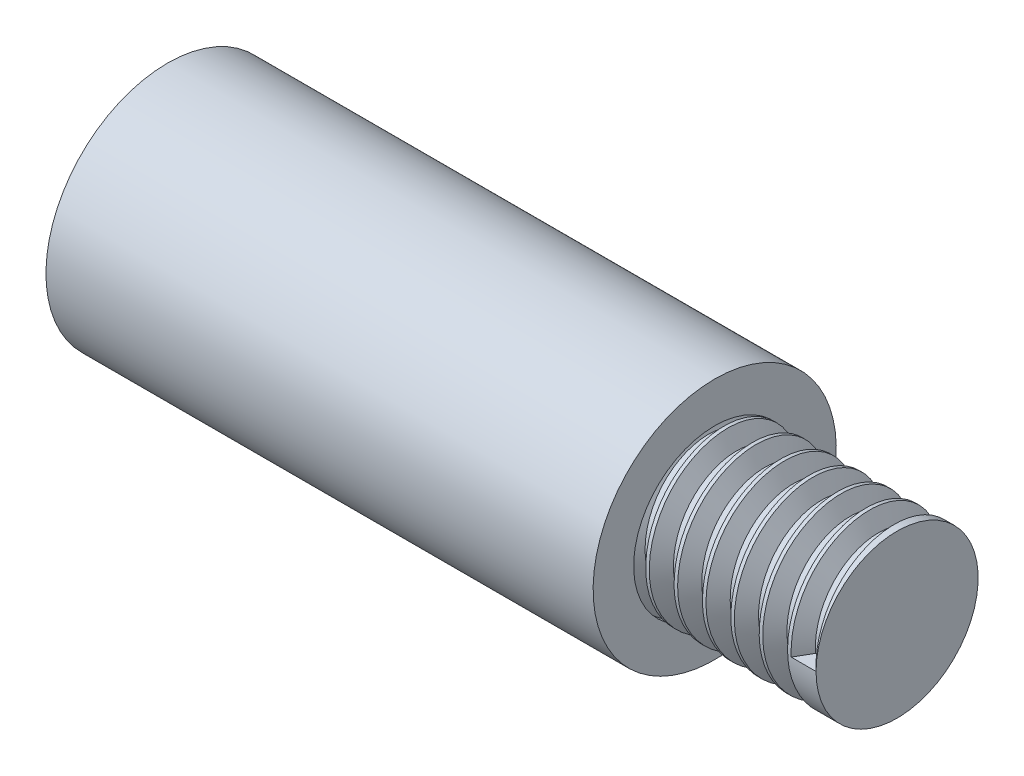
SolidWorks part; units mm, degrees
ref_plane "Front Plane" through (0, 0, 0) normal (0, 0, 1) x (1, 0, 0)
ref_plane "Top Plane" through (0, 0, 0) normal (0, 1, 0) x (1, 0, 0)
ref_plane "Right Plane" through (0, 0, 0) normal (1, 0, 0) x (0, 0, -1)
sketch "Sketch1" plane through (0, 0, 0) normal (0, 0, 1) x (1, 0, 0)
  line L0 (0, 0) -> (0, 3)
  line L1 (0, 3) -> (13.5, 3)
  line L2 (13.5, 3) -> (13.5, 2)
  line L3 (13.5, 2) -> (18, 2)
  line L4 (18, 2) -> (18, 0)
  line L5 (18, 0) -> (0, 0)
  dimension "D1" = 13.5
  dimension "D2" = 4.5
  dimension "D3" = 3
  dimension "D4" = 2
revolve "Revolve1" add sketch "Sketch1" angle 360 about L5
thread "Thread1" pitch 0.7 method cut profile "Thread Profile1" start angle 0, offset 0, length 4.5, pitch 0.7, diameter 4
ref_plane "Plane1" through (18, 0, 2) normal (0, -1, 0) x (0, 0, 1)
sketch "Thread Profile1" plane through (18, 0, 2) normal (0, -1, 0) x (0, 0, 1)
  line L0 (0, 0) -> (0, 0.7) construction
  line L11 (0, 0) -> (0, 0.6125)
  line L12 (0, 0.6125) -> (-0.3789, 0.3937)
  line L13 (-0.3789, 0.3937) -> (-0.3789, 0.2187)
  line L15 (-0.3789, 0.2187) -> (0, 0)
  line L17 (-0.3789, 0.3062) -> (0, 0.3062) construction
  point P2 (0, 0)
  dimension "Pitch" = 0.7
  dimension "Profile_Angle" = 60
  dimension "Profile_Land" = 0.175
  dimension "Profile_Height" = 0.3789
